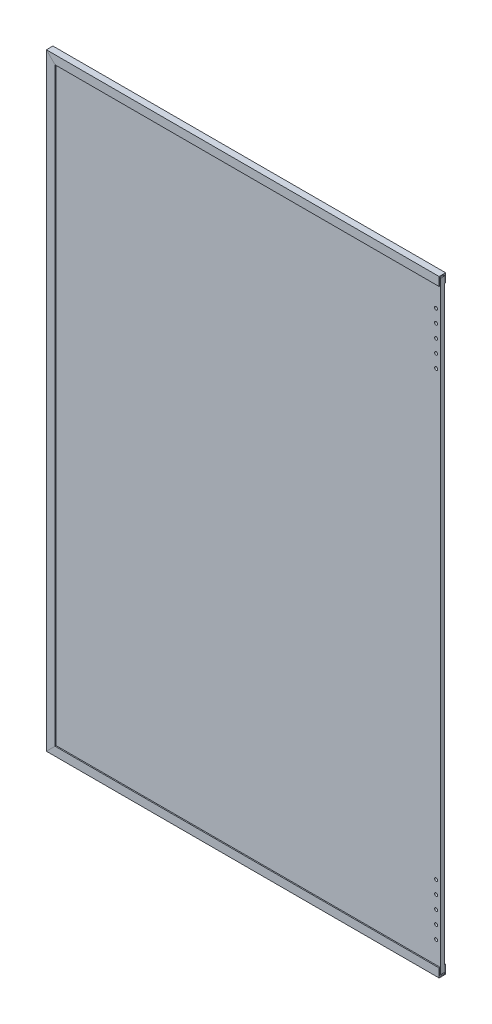
SolidWorks part; units mm, degrees
material "PC High Viscosity"
ref_plane "Front Plane" through (0, 0, 0) normal (0, 0, 1) x (1, 0, 0)
ref_plane "Top Plane" through (0, 0, 0) normal (0, 1, 0) x (1, 0, 0)
ref_plane "Right Plane" through (0, 0, 0) normal (1, 0, 0) x (0, 0, -1)
sketch "Shelf opening" plane through (0, 0, 0) normal (0, 0, 1) x (1, 0, 0)
  line L1 (0, 0) -> (577.85, 0)
  line L2 (0, 0) -> (0, 863.6)
  line L3 (0, 863.6) -> (577.85, 863.6)
  line L4 (577.85, 0) -> (577.85, 863.6)
  dimension "D1" = 577.85
  dimension "D2" = 863.6
sketch "Sketch2" plane through (0, 0, 0) normal (0, 0, 1) x (1, 0, 0)
  line L0 (577.85, 0) -> (577.85, 863.6) construction
  line L1 (3.175, 876.3) -> (577.85, 876.3)
  line L2 (3.175, 876.3) -> (3.175, -12.7)
  line L3 (3.175, -12.7) -> (577.85, -12.7)
  line L4 (577.85, 876.3) -> (577.85, -12.7)
  line L5 (0, 863.6) -> (577.85, 863.6) construction
  line L6 (0, 0) -> (0, 863.6) construction
  line L7 (0, 0) -> (577.85, 0) construction
  dimension "D1" = 12.7
  dimension "D2" = 3.175
  dimension "D3" = 12.7
extrude "Frame outer dimensions" add sketch "Sketch2" along normal mid plane 9.525
sketch "Sketch3" plane through (0, 0, 4.7625) normal (0, 0, 1) x (1, 0, 0)
  line L0 (577.85, -12.7) -> (577.85, 876.3) construction
  line L1 (577.85, 863.6) -> (15.875, 863.6)
  line L2 (577.85, 863.6) -> (577.85, 0)
  line L3 (577.85, 0) -> (15.875, 0)
  line L4 (15.875, 863.6) -> (15.875, 0)
  line L5 (577.85, 876.3) -> (3.175, 876.3) construction
  line L6 (3.175, 876.3) -> (3.175, -12.7) construction
  line L7 (3.175, -12.7) -> (577.85, -12.7) construction
  dimension "D1" = 12.7
  dimension "D2" = 12.7
  dimension "D3" = 12.7
extrude "Frame inner dimensions" cut sketch "Sketch3" against normal through all
sketch "Sketch4" plane through (0, 0, 0) normal (0, 0, 1) x (1, 0, 0)
  line L0 (577.85, 863.6) -> (577.85, 876.3) construction
  line L1 (577.85, 874.7125) -> (4.7625, 874.7125)
  line L2 (577.85, 874.7125) -> (577.85, -11.1125)
  line L3 (577.85, -11.1125) -> (4.7625, -11.1125)
  line L4 (4.7625, 874.7125) -> (4.7625, -11.1125)
  line L5 (577.85, 876.3) -> (3.175, 876.3) construction
  line L6 (3.175, 876.3) -> (3.175, -12.7) construction
  line L7 (3.175, -12.7) -> (577.85, -12.7) construction
  dimension "D1" = 1.5875
  dimension "D2" = 1.5875
  dimension "D3" = 1.5875
extrude "Frame profile" cut sketch "Sketch4" along normal offset from surface 1.5875 and the other way offset from surface 1.5875 up to face at (293.6875, 431.8, 4.7625) other way up to face at (293.6875, 431.8, -4.7625)
sketch "Frame sections" plane through (0, 0, 4.7625) normal (0, 0, 1) x (1, 0, 0)
  line L0 (3.175, 876.3) -> (15.875, 863.6)
  line L1 (3.175, -12.7) -> (15.875, 0)
split "Frame section split" trim tools "Frame sections" bodies to split 103 resulting bodies 105 106 107
sketch "Sketch5" plane through (0, 0, 0) normal (0, 0, 1) x (1, 0, 0)
  line L0 (577.85, 863.6) -> (577.85, 876.3) construction
  line L1 (577.85, 873.125) -> (6.35, 873.125)
  line L2 (577.85, 873.125) -> (577.85, -9.525)
  line L3 (577.85, -9.525) -> (6.35, -9.525)
  line L4 (6.35, 873.125) -> (6.35, -9.525)
  line L5 (4.7625, 874.7125) -> (577.85, 874.7125) construction
  line L6 (4.7625, -11.1125) -> (4.7625, 874.7125) construction
  line L7 (577.85, -11.1125) -> (4.7625, -11.1125) construction
  dimension "D1" = 1.5875
  dimension "D2" = 1.5875
  dimension "D3" = 1.5875
  dimension "D4" = 571.5
  dimension "D5" = 882.65
extrude "Door panel" add sketch "Sketch5" along normal mid plane 5.588 separate body
sketch "Hinge positions" plane through (0, 0, 2.794) normal (0, 0, 1) x (1, 0, 0)
  line L0 (577.85, -9.525) -> (577.85, 873.125) construction
  line L1 (577.85, 841.375) -> (565.15, 841.375)
  line L2 (577.85, 841.375) -> (577.85, 746.125)
  line L3 (577.85, 746.125) -> (565.15, 746.125)
  line L4 (565.15, 841.375) -> (565.15, 746.125)
  line L5 (565.15, 117.475) -> (577.85, 117.475)
  line L6 (565.15, 117.475) -> (565.15, 22.225)
  line L7 (565.15, 22.225) -> (577.85, 22.225)
  line L8 (577.85, 117.475) -> (577.85, 22.225)
  line L10 (0, 0) -> (577.85, 0) construction
  line L11 (0, 863.6) -> (577.85, 863.6) construction
  dimension "D1" = 95.25
  dimension "D2" = 12.7
  dimension "D3" = 22.225
  dimension "D4" = 22.225
  dimension "D5" = 723.9
sketch "Sketch8" plane through (0, 0, 2.794) normal (0, 0, 1) x (1, 0, 0)
  line L0 (565.15, 69.85) -> (577.85, 69.85) construction
  line L2 (565.15, 117.475) -> (565.15, 22.225) construction
  line L3 (577.85, 117.475) -> (577.85, 22.225) construction
  line L4 (565.15, 793.75) -> (577.85, 793.75) construction
  line L6 (565.15, 841.375) -> (565.15, 746.125) construction
  line L7 (577.85, 841.375) -> (577.85, 746.125) construction
  point P0 (571.5, 31.75)
  point P11 (571.5, 50.8)
  point P12 (571.5, 69.85)
  point P13 (571.5, 88.9)
  point P14 (571.5, 107.95)
  point P15 (571.5, 774.7)
  point P16 (571.5, 793.75)
  point P17 (571.5, 812.8)
  point P18 (571.5, 831.85)
  point P19 (571.5, 755.65)
  dimension "D3" = 19.05
  dimension "D1" = 5
  dimension "D2" = 2
hole_wizard "#8 Clearance Hole1" positions "Sketch8" profile "Sketch9" hole size "#8" standard "ANSI Inch" end condition through all
sketch "Sketch9" plane through (571.5, 31.75, 2.794) normal (1, 0, 0) x (0, -1, 0)
  line L0 (0, 0) -> (0, 7.5565)
  line L1 (0, 7.5565) -> (2.2479, 7.5565)
  line L2 (2.2479, 7.5565) -> (2.2479, 0)
  line L5 (2.2479, 0) -> (0, 0)
  line L11 (0, -6.35) -> (0, 107.95) construction
  dimension "Thru Hole Dia." = 4.4958
  dimension "Thru Hole Depth" = 7.5565
mirror "Mirror1" about plane through (0, 0, 0) normal (1, 0, 0) of bodies 105 106 107 108
delete or keep bodies "Body-Delete/Keep 1" type keep bodies bodies 105 106 107 108
delete or keep bodies "Body-Delete/Keep 2" [suppressed] type keep bodies bodies 109 110 111 112
